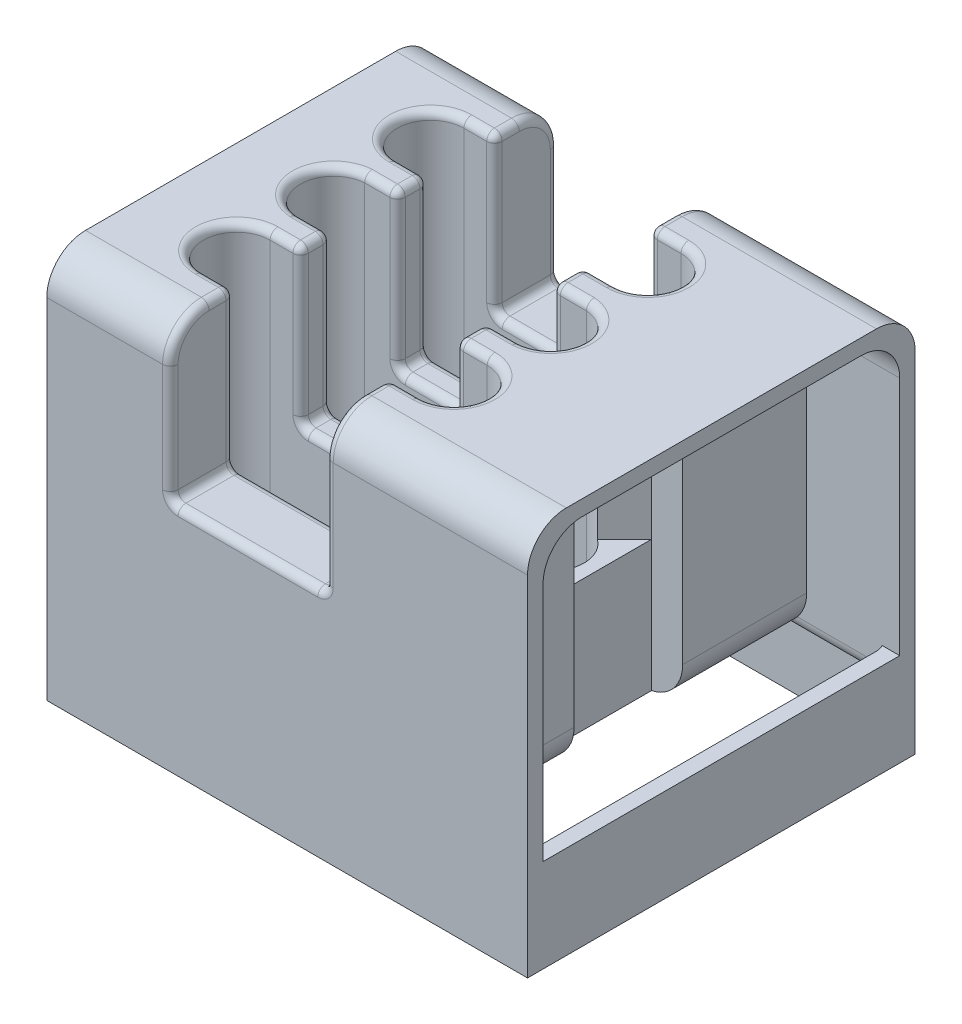
SolidWorks part; units mm, degrees
ref_plane "Front Plane" through (0, 0, 0) normal (0, 0, 1) x (1, 0, 0)
ref_plane "Top Plane" through (0, 0, 0) normal (0, 1, 0) x (1, 0, 0)
ref_plane "Right Plane" through (0, 0, 0) normal (1, 0, 0) x (0, 0, -1)
sketch "Sketch1" plane through (0, 0, 0) normal (0, 1, 0) x (1, 0, 0)
  line L1 (-87.5, 62.5) -> (87.5, 62.5)
  line L2 (-87.5, 62.5) -> (-87.5, -62.5)
  line L3 (-87.5, -62.5) -> (87.5, -62.5)
  line L4 (87.5, 62.5) -> (87.5, -62.5)
  line L5 (-87.5, 62.5) -> (87.5, -62.5) construction
  line L6 (-87.5, -62.5) -> (87.5, 62.5) construction
  point P0 (0, 0)
  dimension "D1" = 125
  dimension "D2" = 175
extrude "Boss-Extrude1" add sketch "Sketch1" along normal blind 140
sketch "Sketch2" plane through (0, 140, 0) normal (0, 1, 0) x (1, 0, 0)
  line L0 (42.5, 62.5) -> (42.5, -62.5) construction
  line L1 (87.5, 62.5) -> (-87.5, 62.5) construction
  line L2 (-87.5, -62.5) -> (87.5, -62.5) construction
  line L3 (87.5, -62.5) -> (87.5, 62.5) construction
  line L4 (-87.5, 0) -> (87.5, 0) construction
  line L5 (-22.5, -62.5) -> (-22.5, 62.5) construction
  line L6 (-57.5, 42) -> (12.5, 42)
  line L7 (-57.5, 20.5) -> (12.5, 20.5)
  line L8 (-87.5, 31.25) -> (42.5, 31.25) construction
  line L9 (-87.5, -31.25) -> (42.5, -31.25) construction
  line L10 (-57.5, -42) -> (12.5, -42)
  line L11 (-57.5, -20.5) -> (12.5, -20.5)
  line L12 (-58.25, 10.75) -> (13.25, 10.75)
  line L13 (-58.25, -10.75) -> (13.25, -10.75)
  arc A0 (-57.5, 20.5) -> (-57.5, 42) centre (-57.5, 31.25) cw
  arc A1 (12.5, 20.5) -> (12.5, 42) centre (12.5, 31.25) ccw
  arc A2 (-57.5, -20.5) -> (-57.5, -42) centre (-57.5, -31.25) ccw
  arc A3 (12.5, -20.5) -> (12.5, -42) centre (12.5, -31.25) cw
  arc A4 (-58.25, 10.75) -> (-58.25, -10.75) centre (-57.4719, 0) ccw
  arc A5 (13.25, 10.75) -> (13.25, -10.75) centre (12.4719, 0) cw
  point P12 (0, 0)
  point P16 (-22.5, 0)
  point P19 (-22.5, 31.25)
  point P24 (-68.25, 31.25)
  point P26 (-22.5, 20.5)
  point P28 (-22.5, 42)
  point P29 (23.25, 31.25)
  point P40 (-68.25, 0)
  point P42 (-22.5, -10.75)
  point P44 (-22.5, 10.75)
  point P45 (23.25, 0)
  dimension "D12" = 10.7781
  dimension "D1" = 45
  dimension "D2" = 65
  dimension "D3" = 62.5
  dimension "D4" = 31.25
  dimension "D5" = 21.5
  dimension "D6" = 0
  dimension "D7" = 91.5
  dimension "D8" = 0
  dimension "D9" = 21.5
  dimension "D10" = 91.5
  dimension "D11" = 10.75
extrude "Cut-Extrude1" cut sketch "Sketch2" against normal blind 100
sketch "Sketch3" plane through (0, 140, 0) normal (0, 1, 0) x (1, 0, 0)
  line L0 (-87.5, -62.5) -> (87.5, -62.5) construction
  line L1 (-47.661, 62.5) -> (2.339, 62.5)
  line L2 (-47.661, 62.5) -> (-47.661, -62.5)
  line L3 (-47.661, -62.5) -> (2.339, -62.5)
  line L4 (2.339, 62.5) -> (2.339, -62.5)
  line L5 (-47.661, 62.5) -> (2.339, -62.5) construction
  line L6 (-47.661, -62.5) -> (2.339, 62.5) construction
  line L7 (-87.5, 62.5) -> (-87.5, -62.5) construction
  point P0 (-22.661, 0)
  dimension "D1" = 50
  dimension "D2" = 125
  dimension "D3" = 39.839
extrude "Cut-Extrude2" cut sketch "Sketch3" against normal blind 50
sketch "Sketch4" plane through (0, 0, 0) normal (0, -1, 0) x (1, 0, 0)
  line L1 (-85, 60) -> (85, 60)
  line L2 (-85, 60) -> (-85, -60)
  line L3 (-85, -60) -> (85, -60)
  line L4 (85, 60) -> (85, -60)
  line L5 (-85, 60) -> (85, -60) construction
  line L6 (-85, -60) -> (85, 60) construction
  point P0 (0, 0)
  dimension "D1" = 170
  dimension "D2" = 120
extrude "Cut-Extrude3" cut sketch "Sketch4" against normal blind 35
sketch "Sketch5" plane through (87.5, 0, 0) normal (1, 0, 0) x (0, 0, -1)
  line L0 (-62.5, 140) -> (62.5, 140) construction
  line L1 (-57.5, 135) -> (57.5, 135)
  line L2 (-57.5, 135) -> (-57.5, 45)
  line L3 (-57.5, 45) -> (57.5, 45)
  line L4 (57.5, 135) -> (57.5, 45)
  line L5 (-57.5, 135) -> (57.5, 45) construction
  line L6 (-57.5, 45) -> (57.5, 135) construction
  line L8 (62.5, 140) -> (62.5, 0) construction
  point P0 (0, 90)
  dimension "D1" = 90
  dimension "D2" = 115
  dimension "D3" = 5
  dimension "D4" = 5
extrude "Cut-Extrude4" cut sketch "Sketch5" against normal blind 50
sketch "Sketch6" plane through (0, 35, 0) normal (0, -1, 0) x (1, 0, 0)
  line L5 (-87.5, 62.5) -> (87.5, 62.5) construction
  line L6 (37.5, 57.5) -> (82.5, 57.5)
  line L8 (37.5, 57.5) -> (37.5, -57.5)
  line L9 (37.5, -57.5) -> (82.5, -57.5)
  line L10 (82.5, 57.5) -> (82.5, -57.5)
  line L11 (37.5, 57.5) -> (82.5, -57.5) construction
  line L12 (37.5, -57.5) -> (82.5, 57.5) construction
  line L13 (87.5, -62.5) -> (-87.5, -62.5) construction
  line L14 (87.5, 62.5) -> (87.5, -62.5) construction
  point P0 (60, 0)
  dimension "D1" = 5
  dimension "D2" = 5
  dimension "D3" = 45
  dimension "D4" = 5
extrude "Cut-Extrude5" cut sketch "Sketch6" against normal blind 11
sketch "Sketch7" plane through (37.5, 0, 0) normal (1, 0, 0) x (0, 0, -1)
  line L0 (62.5, 140) -> (62.5, 0) construction
  line L1 (-17.5, 122.5) -> (17.5, 122.5)
  line L2 (-17.5, 122.5) -> (-17.5, 32.5)
  line L3 (-17.5, 32.5) -> (17.5, 32.5)
  line L4 (17.5, 122.5) -> (17.5, 32.5)
  line L5 (-17.5, 122.5) -> (17.5, 32.5) construction
  line L6 (-17.5, 32.5) -> (17.5, 122.5) construction
  line L10 (-62.5, 140) -> (62.5, 140) construction
  point P0 (0, 77.5)
  dimension "D1" = 62.5
  dimension "D2" = 17.5
  dimension "D3" = 35
  dimension "D4" = 90
extrude "Cut-Extrude6" cut sketch "Sketch7" against normal blind 10
sketch "Sketch8" plane through (27.5, 0, 0) normal (1, 0, 0) x (0, 0, -1)
  line L0 (-17.5, 122.5) -> (-17.5, 35) construction
  line L1 (-17.5, 112.5) -> (17.5, 112.5)
  line L2 (-17.5, 112.5) -> (-17.5, 77.5)
  line L3 (-17.5, 77.5) -> (17.5, 77.5)
  line L4 (17.5, 112.5) -> (17.5, 77.5)
  line L5 (-17.5, 112.5) -> (17.5, 77.5) construction
  line L6 (-17.5, 77.5) -> (17.5, 112.5) construction
  line L8 (17.5, 122.5) -> (-17.5, 122.5) construction
  point P0 (0, 95)
  dimension "D1" = 35
  dimension "D2" = 35
  dimension "D3" = 17.5
  dimension "D4" = 10
extrude "Cut-Extrude7" cut sketch "Sketch8" against normal blind 10
sketch "Sketch9" plane through (0, 35, 0) normal (0, -1, 0) x (1, 0, 0)
  line L1 (-85, -60) -> (-2.7, -60)
  line L2 (-85, -60) -> (-85, 10.1)
  line L3 (-85, 10.1) -> (-2.7, 10.1) construction
  line L4 (-2.7, -60) -> (-2.7, 10.1) construction
  circle A0 centre (-13.7, -57.2) radius 1
  circle A1 centre (-77.2, -57.2) radius 1
  circle A2 centre (-13.7, 6.55) radius 1
  circle A3 centre (-77.2, 6.55) radius 1
  dimension "D3" = 2
  dimension "D6" = 2
  dimension "D9" = 2
  dimension "D11" = 3.55
  dimension "D12" = 2
  dimension "D1" = 70.1
  dimension "D2" = 82.3
  dimension "D4" = 11
  dimension "D5" = 2.8
  dimension "D7" = 63.5
  dimension "D8" = 2.8
  dimension "D10" = 63.75
  dimension "D13" = 3.55
  dimension "D14" = 63.5
extrude "Cut-Extrude8" cut sketch "Sketch9" against normal blind 3 contours A0 | A1 | A3 | A2 region at (-13.7, 35, -57.2) region at (-77.2, 35, -57.2) region at (-13.7, 35, 6.55) region at (-77.2, 35, 6.55)
sketch "Sketch11" plane through (0, 0, 0) normal (0, -1, 0) x (1, 0, 0)
  line L0 (-85, 60) -> (-85, -60) construction
  line L1 (-87.5, 62.5) -> (87.5, 62.5)
  line L2 (-87.5, 62.5) -> (-87.5, -62.5)
  line L3 (-87.5, -62.5) -> (87.5, -62.5)
  line L4 (87.5, 62.5) -> (87.5, -62.5)
  line L5 (-85, -60) -> (85, -60) construction
  line L6 (-87.5, 0) -> (87.5, 0) construction
  line L7 (0, 62.5) -> (0, -62.5) construction
  line L8 (-85, 55.5) -> (-85, -55.5)
  line L9 (-80.5, 60) -> (80.5, 60)
  line L10 (85, 60) -> (-85, 60) construction
  line L11 (-80.5, -60) -> (80.5, -60)
  line L12 (-85, -60) -> (85, -60) construction
  line L13 (85, 55.5) -> (85, -55.5)
  line L15 (-87.5, 62.5) -> (87.5, 62.5)
  line L16 (-87.5, 62.5) -> (-87.5, -62.5)
  line L17 (-87.5, -62.5) -> (87.5, -62.5)
  line L18 (87.5, 62.5) -> (87.5, -62.5)
  arc A0 (-85, -55.5) -> (-80.5, -60) centre (-85, -60) cw
  arc A1 (-85, 55.5) -> (-80.5, 60) centre (-85, 60) ccw
  arc A2 (85, -55.5) -> (80.5, -60) centre (85, -60) ccw
  arc A3 (85, 55.5) -> (80.5, 60) centre (85, 60) cw
  point P17 (0, 0)
  point P21 (0, 0)
  point P31 (0, -60)
  point P36 (0, 60)
  line M15 (-85, 60) -> (85, 60)
  line M16 (85, 60) -> (85, -60)
  line M17 (85, -60) -> (-85, -60)
  line M18 (-85, -60) -> (-85, 60)
  line M19 (87.5, -62.5) -> (87.5, 62.5)
  line M20 (87.5, 62.5) -> (-87.5, 62.5)
  line M21 (-87.5, 62.5) -> (-87.5, -62.5)
  line M22 (-87.5, -62.5) -> (87.5, -62.5)
  dimension "D1" = 4.5
  dimension "D2" = 2.5
  dimension "D3" = 2.5
extrude "Boss-Extrude2" add sketch "Sketch11" against normal blind 45 contours A1 M18 M15 | M22 M19 M20 M21 M18 M15 M16 M17 | A0 M18 M17 | A2 M16 M17 | A3 M16 M15 region at (0, 0, 60.3494) region at (-83.0901, 0, 58.0901) region at (-83.0901, 0, -58.0901) region at (83.0901, 0, 58.0901) region at (83.0901, 0, -58.0901)
sketch "Sketch10" plane through (0, 0, -62.5) normal (0, 0, -1) x (-1, 0, 0)
  line L0 (87.5, 140) -> (87.5, 0) construction
  line L1 (20.75, 30.4) -> (33.5, 30.4)
  line L2 (20.75, 30.4) -> (20.75, 24.9)
  line L3 (20.75, 24.9) -> (33.5, 24.9)
  line L4 (33.5, 30.4) -> (33.5, 24.9)
  line L6 (-87.5, 0) -> (87.5, 0) construction
  line L7 (35.0875, 90) -> (35.0875, 0) construction
  line L8 (-2.339, 90) -> (47.661, 90) construction
  line L9 (49.425, 24.9) -> (36.675, 24.9)
  line L10 (36.675, 30.4) -> (36.675, 24.9)
  line L11 (49.425, 30.4) -> (36.675, 30.4)
  line L12 (49.425, 30.4) -> (49.425, 24.9)
  point P6 (33.5, 27.65)
  dimension "D1" = 66.75
  dimension "D2" = 30.4
  dimension "D3" = 5.5
  dimension "D4" = 12.75
  dimension "D5" = 1.5875
extrude "Cut-Extrude9" cut sketch "Sketch10" against normal up to next
sketch "Sketch13" plane through (0, 0, 0) normal (0, -1, 0) x (1, 0, 0)
  line L1 (-87.5, 62.5) -> (87.5, 62.5)
  line L2 (-87.5, 62.5) -> (-87.5, -62.5)
  line L3 (-87.5, -62.5) -> (87.5, -62.5)
  line L4 (87.5, 62.5) -> (87.5, -62.5)
extrude "Cut-Extrude10" cut sketch "Sketch13" against normal blind 15
fillet "Fillet3" radius 12.5 6 edges at (-67.5805, 140, -62.5) (-67.5805, 140, 62.5) (44.9195, 140, -62.5) (44.9195, 140, 62.5) (62.5, 135, -57.5) (62.5, 135, 57.5)
chamfer "Chamfer1" distance 10 angle 45 2 edges at (17.5, 95, -17.5) (17.5, 95, 17.5)
sketch "Sketch16" plane through (87.5, 0, 0) normal (1, 0, 0) x (0, 0, -1)
  line L0 (-57.5, 122.5) -> (-57.5, 45)
  line L1 (-62.5, 15) -> (62.5, 15)
  line L2 (-62.5, 15) -> (-62.5, 140)
  line L3 (-62.5, 140) -> (62.5, 140)
  line L4 (62.5, 15) -> (62.5, 140)
  line L5 (0, 77.5) -> (0, 50077.5) construction
  line L6 (-17.5, 77.5) -> (17.5, 77.5) construction
  line L7 (-57.5, 45) -> (57.5, 45)
  line L8 (-57.5, 45) -> (57.5, 45) construction
  line L9 (0, 15) -> (-62.5, 15)
  line L10 (-62.5, 15) -> (-62.5, 127.5)
  line L11 (-50, 140) -> (0, 140)
  line L12 (-45, 135) -> (45, 135)
  line L13 (45, 135) -> (-45, 135) construction
  line L14 (62.5, 15) -> (62.5, 140)
  line L15 (57.5, 122.5) -> (57.5, 45)
  arc A1 (-50, 140) -> (-62.5, 127.5) centre (-50, 127.5) ccw
  arc A2 (-57.5, 122.5) -> (-45, 135) centre (-45, 122.5) cw
  arc A3 (50, 140) -> (62.5, 127.5) centre (50, 127.5) cw
  arc A4 (57.5, 122.5) -> (45, 135) centre (45, 122.5) ccw
  point P21 (0, 77.5)
  point P31 (0, 45)
  point P37 (0, 135)
  line M12 (57.5, 122.5) -> (57.5, 45)
  line M13 (57.5, 45) -> (-57.5, 45)
  line M14 (-57.5, 45) -> (-57.5, 122.5)
  arc M15 (-57.5, 122.5) -> (-45, 135) centre (-45, 122.5) cw
  line M16 (-45, 135) -> (45, 135)
  arc M17 (45, 135) -> (57.5, 122.5) centre (45, 122.5) cw
  line M18 (62.5, 15) -> (62.5, 127.5)
  arc M19 (62.5, 127.5) -> (50, 140) centre (50, 127.5) ccw
  line M20 (50, 140) -> (-50, 140)
  arc M21 (-50, 140) -> (-62.5, 127.5) centre (-50, 127.5) ccw
  line M22 (-62.5, 127.5) -> (-62.5, 15)
  line M23 (-62.5, 15) -> (62.5, 15)
extrude "Boss-Extrude3" add sketch "Sketch16" against normal blind 25 contours L5 L7 L3 M23 M14 M15 M16 M21 M22 | L5 L1 L12 M18 M19 M20 M17 M12 M13 region at (87.5, 138.2322, -25)
sketch "Sketch17" plane through (87.5, 0, 0) normal (1, 0, 0) x (0, 0, -1)
  line L1 (-62.5, 15) -> (62.5, 15)
  line L2 (-62.5, 15) -> (-62.5, 140)
  line L3 (-62.5, 140) -> (62.5, 140)
  line L4 (62.5, 15) -> (62.5, 140)
extrude "Cut-Extrude11" cut sketch "Sketch17" against normal blind 20
fillet "Fillet5" radius 12.5 1 edges at (37.5, 35, -37.5)
sketch "Sketch18" plane through (0, 15, 0) normal (0, -1, 0) x (1, 0, 0)
  line L0 (67.5, 62.5) -> (-87.5, 62.5) construction
  line L1 (-87.5, 62.5) -> (-87.5, -62.5) construction
  line L2 (0, 0) -> (50000, 0) construction
  line L3 (-10, 62.5) -> (-10, -49937.5) construction
  circle A0 centre (-84, 59) radius 1.5
  circle A1 centre (-84, -59) radius 1.5
  circle A2 centre (64, -59) radius 1.5
  circle A3 centre (64, 59) radius 1.5
  point P11 (-10, 62.5)
  dimension "D1" = 3
  dimension "D2" = 3.5
  dimension "D3" = 3.5
fillet "Fillet6" radius 5 2 edges at (62.5, 25, -60) (62.5, 25, 60)
fillet "Fillet7" radius 5 2 edges at (43.4151, 35, 57.5) (43.4151, 35, -57.5)
extrude "Cut-Extrude12" cut sketch "Sketch18" against normal blind 10
fillet "Fillet8" radius 2.5 44 edges at (-22.661, 90, 62.5) (-22.661, 90, 42) (-22.661, 90, 10.75) (-22.661, 90, 20.5) (-22.661, 90, -10.75) (-22.661, 90, -20.5) (-22.661, 90, -42) (-22.661, 90, -62.5) (-47.661, 115, 10.75) (-47.661, 90, 15.625) (-47.661, 115, 20.5) (-47.661, 140, 15.625) (-47.661, 115, 42) (-47.661, 90, 52.25) (-47.661, 108.75, 62.5) (-47.661, 136.3388, 58.8388) (-47.661, 140, 46) (2.339, 90, 52.25) (2.339, 115, 42) (2.339, 140, 46) (2.339, 136.3388, 58.8388) (2.339, 108.75, 62.5) (2.339, 115, 10.75) (2.339, 140, 15.625) (2.339, 115, 20.5) (2.339, 90, 15.625) (2.339, 115, -10.75) (2.339, 90, -15.625) (2.339, 115, -20.5) (2.339, 140, -15.625) (-47.661, 115, -10.75) (-47.661, 140, -15.625) (-47.661, 115, -20.5) (-47.661, 90, -15.625) (-47.661, 90, -52.25) (-47.661, 115, -42) (-47.661, 140, -46) (-47.661, 136.3388, -58.8388) (-47.661, 108.75, -62.5) (2.339, 115, -42) (2.339, 90, -52.25) (2.339, 108.75, -62.5) (2.339, 136.3388, -58.8388) (2.339, 140, -46)
fillet "Fillet9" radius 2.5 30 edges at (-48.3932, 139.2678, -11.4822) (-48.3932, 139.2678, 11.4822) (-48.3932, 139.2678, -42.7322) (-53.8305, 140, -42) (-48.3932, 139.2678, -19.7678) (-53.8305, 140, -20.5) (-48.3932, 139.2678, 19.7678) (-53.8305, 140, 20.5) (-48.3932, 139.2678, 42.7322) (-53.8305, 140, 42) (3.0713, 139.2678, -19.7678) (8.6695, 140, -20.5) (3.0713, 139.2678, -42.7322) (8.6695, 140, -42) (3.0713, 139.2678, 11.4822) (3.0713, 139.2678, 42.7322) (8.6695, 140, 42) (3.0713, 139.2678, 19.7678) (8.6695, 140, 20.5) (-54.2055, 140, -10.75) (-54.2055, 140, 10.75) (-68.25, 140, 0) (-68.25, 140, -31.25) (-68.25, 140, 31.25) (23.25, 140, -31.25) (9.0445, 140, 10.75) (23.25, 140, 0) (23.25, 140, 31.25) (3.0713, 139.2678, -11.4822) (9.0445, 140, -10.75)
